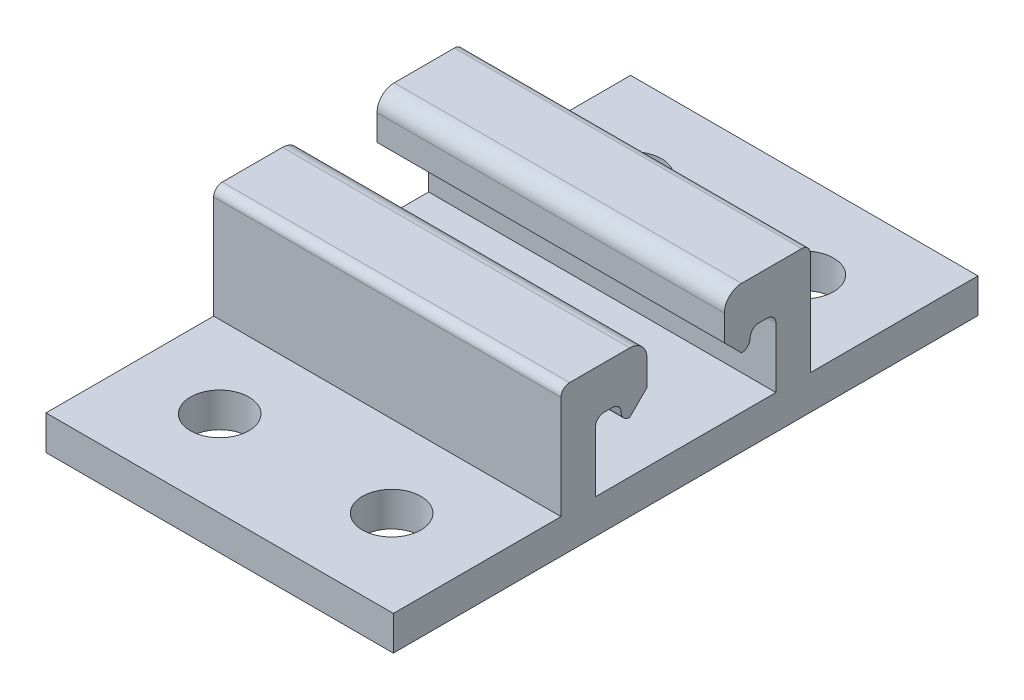
SolidWorks part; units mm, degrees
material "Lega 1060"
ref_plane "Piano frontale" through (0, 0, 0) normal (0, 0, 1) x (1, 0, 0)
ref_plane "Piano superiore" through (0, 0, 0) normal (0, 1, 0) x (1, 0, 0)
ref_plane "Piano destro" through (0, 0, 0) normal (1, 0, 0) x (0, 0, -1)
sketch "Schizzo1" plane through (0, 0, 0) normal (0, 1, 0) x (1, 0, 0)
  line L1 (-10.1, -17) -> (10.1, -17)
  line L2 (-10.1, -17) -> (-10.1, 17)
  line L3 (-10.1, 17) -> (10.1, 17)
  line L4 (10.1, -17) -> (10.1, 17)
  line L5 (-10.1, -17) -> (10.1, 17) construction
  line L6 (-10.1, 17) -> (10.1, -17) construction
  point P0 (0, 0)
  dimension "D1" = 20.2
  dimension "D2" = 34
extrude "Estrusione-Estrusione1" add sketch "Schizzo1" along normal blind 2
sketch "Schizzo3" plane through (10.1, 0, 0) normal (1, 0, 0) x (0, 0, -1)
  line L0 (-17, 2) -> (17, 2) construction
  line L1 (-7.25, 2) -> (-5.25, 2)
  line L2 (-7.25, 2) -> (-7.25, 8.5)
  line L3 (-7.25, 8.5) -> (-2.25, 8.5)
  line L4 (-2.25, 8.5) -> (-2.25, 5)
  line L5 (-5.25, 6) -> (-3.75, 6)
  line L6 (-5.25, 6) -> (-5.25, 2)
  line L8 (-2.25, 7.25) -> (-7.25, 7.25) construction
  line L9 (-3.75, 6) -> (-3.75, 5)
  line L10 (-3.75, 5) -> (-2.25, 5)
  line L11 (-4.5, 6) -> (-4.5, 7.25) construction
  line L12 (-4.5, 7.25) -> (-4.5, 8.5) construction
  line L13 (0, 0) -> (0, 14.8374) construction
  dimension "D1" = 10.5
  dimension "D2" = 6.5
  dimension "D3" = 2.5
  dimension "D4" = 4.5
  dimension "D5" = 1.5
  dimension "D6" = 2
  dimension "D7" = 3
extrude "Estrusione-Estrusione2" add sketch "Schizzo3" against normal up to surface (20.2 mm away) up to face at (-10.1, 1, 0)
chamfer "Smusso1" distance 1 angle 45 1 edges at (0, 5, 2.25)
fillet "Raccordo2" radius 0.5 4 edges at (0, 8.5, 7.25) (0, 6, 5.25) (0, 6, 3.75) (0, 5, 3.75)
fillet "Raccordo3" radius 1 1 edges at (0, 8.5, 2.25)
hole_wizard "Foro per Vite M3-1" positions "Schizzo5" profile "Schizzo4" hole size "M3" standard "Ansi Metric" end condition through all
sketch "Schizzo5" plane through (0, 2, 0) normal (0, 1, 0) x (1, 0, 0)
  line L0 (-10.1, -12) -> (-5, -12) construction
  line L1 (-10.1, -7.25) -> (-10.1, -17) construction
  line L2 (-5, -12) -> (5, -12) construction
  line L3 (5, -12) -> (10.1, -12) construction
  line L5 (0, 0) -> (0, -12) construction
  line L7 (-5, -12) -> (-5, -17) construction
  line L8 (-10.1, -17) -> (10.1, -17) construction
  point P0 (-5, -12)
  point P2 (5, -12)
  dimension "D1" = 5
  dimension "D2" = 10
sketch "Schizzo4" plane through (-5, 2, 12) normal (1, 0, 0) x (0, 0, 1)
  line L0 (0, 0) -> (0, 2)
  line L1 (0, 2) -> (1.7, 2)
  line L2 (1.7, 2) -> (1.7, 0)
  line L5 (1.7, 0) -> (0, 0)
  line L11 (0, -6.35) -> (0, 107.95) construction
  dimension "Thru Hole Dia." = 3.4
  dimension "Thru Hole Depth" = 2
mirror "Specchia2" about plane through (0, 0, 0) normal (0, 0, 1) of "Raccordo3", "Estrusione-Estrusione2", "Smusso1", "Raccordo2", "Foro per Vite M3-1"
